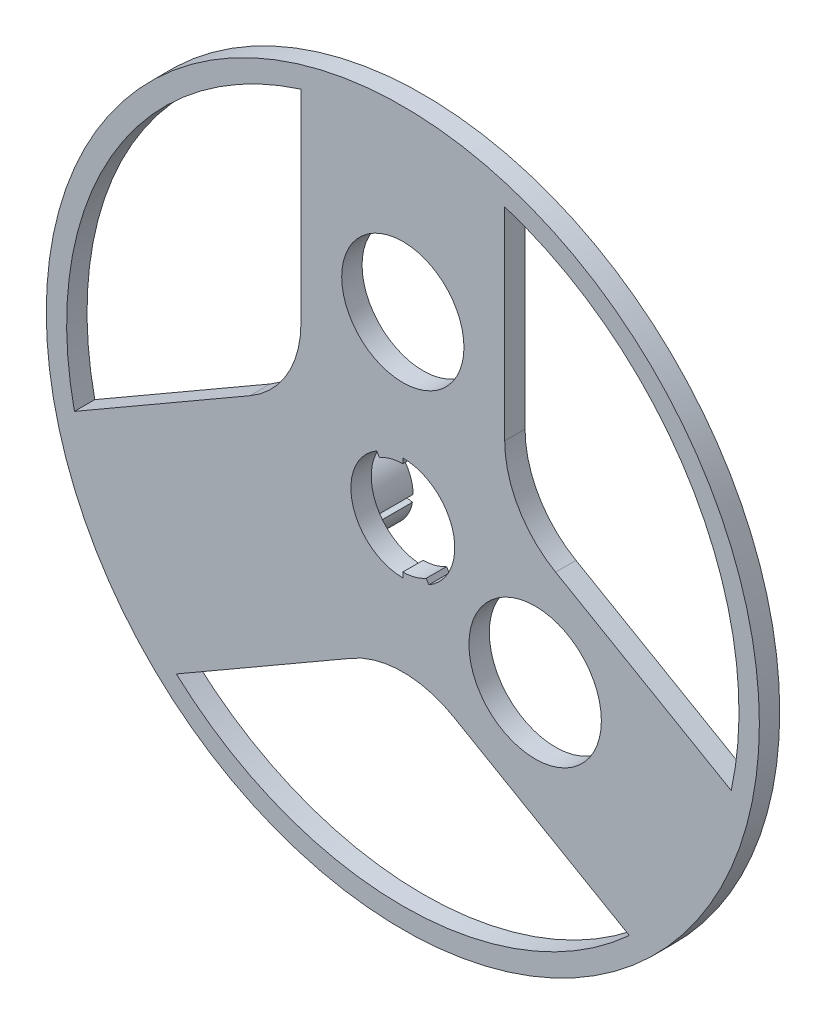
SolidWorks part; units mm, degrees
ref_plane "Front Plane" through (0, 0, 0) normal (0, 0, 1) x (1, 0, 0)
ref_plane "Top Plane" through (0, 0, 0) normal (0, 1, 0) x (1, 0, 0)
ref_plane "Right Plane" through (0, 0, 0) normal (1, 0, 0) x (0, 0, -1)
sketch "Sketch1" plane through (0, 0, 0) normal (0, 0, 1) x (1, 0, 0)
  line L0 (0, 0) -> (0, 33) construction
  line L1 (0, 0) -> (-10, 5.7735)
  line L2 (-10, 5.7735) -> (-10, 31.4484)
  line L3 (0, 0) -> (10, 5.7735)
  line L4 (10, 5.7735) -> (10, 31.4484)
  line L5 (10, 5.7735) -> (32.2351, -7.0639)
  line L6 (0, -11.547) -> (22.2351, -24.3844)
  line L7 (0, 0) -> (0, -11.547)
  line L8 (0, 0) -> (10, 5.7735)
  line L9 (0, -11.547) -> (-22.2351, -24.3844)
  line L10 (-10, 5.7735) -> (-32.2351, -7.0639)
  line L11 (0, 0) -> (-10, 5.7735)
  line L12 (0, 0) -> (0, -11.547)
  circle A0 centre (0, 0) radius 35
  circle A2 centre (0, 0) radius 33
  point P20 (0, 0)
  dimension "D1" = 70
  dimension "D2" = 10
  dimension "D3" = 66
  dimension "D4" = 60
  dimension "D5" = 3
extrude "Boss-Extrude1" add sketch "Sketch1" along normal blind 2 contours L1 L0 A2 L2 | L0 L3 L4 A2 | L6 A2 L5 L3 L7 | L10 A2 L9 L7 L1 | A0 A2 L9 region at (-4.794, 17.6439, 0) region at (-15.2801, -8.822, 0) region at (4.794, 17.6439, 0) region at (15.2801, -8.822, 0) region at (-34.0101, 0, 0)
fillet "Fillet1" radius 10 3 edges at (10, 5.7735, 1) (0, -11.547, 1) (-10, 5.7735, 1)
sketch "Sketch3" plane through (0, 0, 0) normal (0, 0, -1) x (-1, 0, 0)
  line L0 (0, 0) -> (0, 35) construction
  line L1 (0, 0) -> (30.3109, -17.5) construction
  line L2 (0, 0) -> (-30.3109, -17.5) construction
  line L3 (-5, -14.4338) -> (-22.2351, -24.3844) construction
  line L4 (5, -14.4338) -> (22.2351, -24.3844) construction
  line L5 (12.9904, -7.5) -> (12.9904, -3.5)
  line L6 (12.9904, -7.5) -> (16.9296, -6.8054)
  line L7 (12.9904, -7.5) -> (13.685, -11.4392)
  line L8 (12.9904, -7.5) -> (16.9904, -7.5)
  line L9 (12.9904, -7.5) -> (9.0512, -8.1946)
  line L10 (12.9904, -7.5) -> (12.9904, -11.5)
  line L11 (12.9904, -7.5) -> (12.2958, -3.5608)
  line L12 (12.9904, -7.5) -> (8.9904, -7.5)
  circle A0 centre (0, 0) radius 15 construction
  circle A1 centre (0, 0) radius 35 construction
  circle A2 centre (0, 17.5) radius 6
  circle A3 centre (-12.9904, -7.5) radius 6.5
  circle A4 centre (12.9904, -7.5) radius 3.4
  circle A5 centre (12.9904, -7.5) radius 4
  point P31 (12.9904, -7.5)
  dimension "D1" = 30
  dimension "D2" = 12
  dimension "D3" = 13
  dimension "D4" = 6.8
  dimension "D5" = 8
  dimension "D6" = 80
  dimension "D7" = 4
sketch "Sketch2" plane through (0, 0, 0) normal (0, 0, -1) x (-1, 0, 0)
  line L0 (0, 0) -> (0, 35) construction
  line L1 (0, 0) -> (0, 5.1) construction
  line L2 (0, 0) -> (2.55, 4.4167) construction
  line L3 (0, 5.1) -> (0, 4.6)
  line L4 (2.55, 4.4167) -> (2.3, 3.9837)
  line L5 (0, -5.1) -> (0, -4.6)
  line L6 (-2.55, -4.4167) -> (-2.3, -3.9837)
  circle A0 centre (0, 0) radius 5.1
  circle A1 centre (0, 0) radius 35 construction
  circle A2 centre (0, 0) radius 4.6
  point P19 (0, 0)
  dimension "D1" = 10.2
  dimension "D2" = 9.2
  dimension "D4" = 30
  dimension "D5" = 2
extrude "Cut-Extrude2" cut sketch "Sketch2" against normal up to next contours A2 | A2 L5 A0 L4 | A2 L3 A0 L6 region at (0.108, 4.85, 0) region at (0, 0, 0) region at (-4.3232, 2.496, 0)
extrude "Cut-Extrude3" cut sketch "Sketch3" against normal up to next contours A3 | A2 region at (0, 17.5, 0) region at (12.9904, -7.5, 0)
extrude "Boss-Extrude2" add sketch "Sketch3<4>" along normal blind 8 contours L7 A5 L8 A4 | L6 A5 L5 A4 | L11 A5 L12 A4 | L9 A5 L10 A4 region at (-15.185, -4.8846, 0) region at (-15.6058, -9.6946, 0) region at (-10.7958, -10.1154, 0) region at (-10.375, -5.3054, 0)
sketch "Sketch3<4>" plane through (0, 0, 0) normal (0, 0, -1) x (-1, 0, 0) same geometry as "Sketch3"
